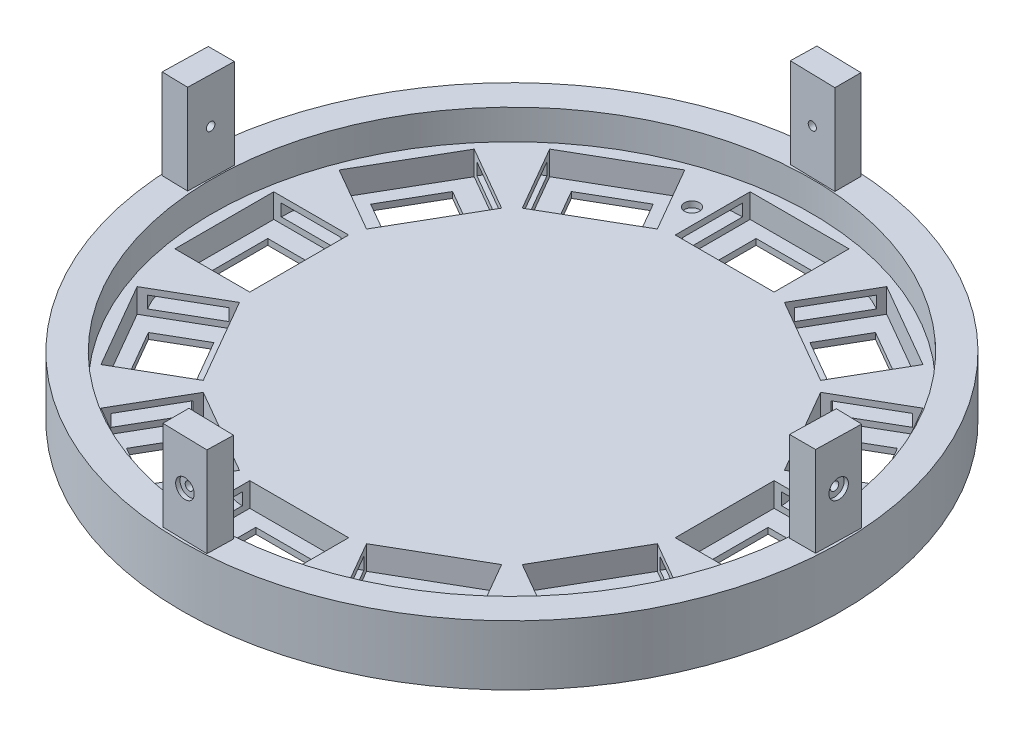
SolidWorks part; units mm, degrees
material "Pine"
ref_plane "Front Plane" through (0, 0, 0) normal (0, 0, 1) x (1, 0, 0)
ref_plane "Top Plane" through (0, 0, 0) normal (0, 1, 0) x (1, 0, 0)
ref_plane "Right Plane" through (0, 0, 0) normal (1, 0, 0) x (0, 0, -1)
sketch "Sketch2" plane through (0, 0, 0) normal (0, 1, 0) x (1, 0, 0)
  circle A0 centre (0, 0) radius 55
  dimension "D1" = 110
extrude "Boss-Extrude1" add sketch "Sketch2" along normal blind 10
sketch "Sketch3" plane through (0, 10, 0) normal (0, 1, 0) x (1, 0, 0)
  circle A3 centre (0, 0) radius 50
  circle A4 centre (0, 0) radius 50
  dimension "D1" = 5
extrude "Cut-Extrude1" cut sketch "Sketch3" against normal blind 5
sketch "Sketch4" plane through (0, 5, 0) normal (0, 1, 0) x (1, 0, 0)
  line L0 (0, 0) -> (0, 50) construction
  line L5 (-8.25, 48) -> (8.25, 48)
  line L6 (-8.25, 48) -> (-8.25, 35.5)
  line L7 (-8.25, 35.5) -> (8.25, 35.5)
  line L8 (8.25, 48) -> (8.25, 35.5)
  line L37 (16.8553, 45.6942) -> (10.6053, 34.8689)
  line L38 (16.8553, 45.6942) -> (31.1447, 37.4442)
  line L39 (31.1447, 37.4442) -> (24.8947, 26.6189)
  line L40 (10.6053, 34.8689) -> (24.8947, 26.6189)
  line L41 (37.4442, 31.1447) -> (26.6189, 24.8947)
  line L42 (37.4442, 31.1447) -> (45.6942, 16.8553)
  line L43 (45.6942, 16.8553) -> (34.8689, 10.6053)
  line L44 (26.6189, 24.8947) -> (34.8689, 10.6053)
  line L45 (48, 8.25) -> (35.5, 8.25)
  line L46 (48, 8.25) -> (48, -8.25)
  line L47 (48, -8.25) -> (35.5, -8.25)
  line L48 (35.5, 8.25) -> (35.5, -8.25)
  line L49 (45.6942, -16.8553) -> (34.8689, -10.6053)
  line L50 (45.6942, -16.8553) -> (37.4442, -31.1447)
  line L51 (37.4442, -31.1447) -> (26.6189, -24.8947)
  line L52 (34.8689, -10.6053) -> (26.6189, -24.8947)
  line L53 (31.1447, -37.4442) -> (24.8947, -26.6189)
  line L54 (31.1447, -37.4442) -> (16.8553, -45.6942)
  line L55 (16.8553, -45.6942) -> (10.6053, -34.8689)
  line L56 (24.8947, -26.6189) -> (10.6053, -34.8689)
  line L57 (8.25, -48) -> (8.25, -35.5)
  line L58 (8.25, -48) -> (-8.25, -48)
  line L59 (-8.25, -48) -> (-8.25, -35.5)
  line L60 (8.25, -35.5) -> (-8.25, -35.5)
  line L61 (-16.8553, -45.6942) -> (-10.6053, -34.8689)
  line L62 (-16.8553, -45.6942) -> (-31.1447, -37.4442)
  line L63 (-31.1447, -37.4442) -> (-24.8947, -26.6189)
  line L64 (-10.6053, -34.8689) -> (-24.8947, -26.6189)
  line L65 (-37.4442, -31.1447) -> (-26.6189, -24.8947)
  line L66 (-37.4442, -31.1447) -> (-45.6942, -16.8553)
  line L67 (-45.6942, -16.8553) -> (-34.8689, -10.6053)
  line L68 (-26.6189, -24.8947) -> (-34.8689, -10.6053)
  line L69 (-48, -8.25) -> (-35.5, -8.25)
  line L70 (-48, -8.25) -> (-48, 8.25)
  line L71 (-48, 8.25) -> (-35.5, 8.25)
  line L72 (-35.5, -8.25) -> (-35.5, 8.25)
  line L73 (-45.6942, 16.8553) -> (-34.8689, 10.6053)
  line L74 (-45.6942, 16.8553) -> (-37.4442, 31.1447)
  line L75 (-37.4442, 31.1447) -> (-26.6189, 24.8947)
  line L76 (-34.8689, 10.6053) -> (-26.6189, 24.8947)
  line L77 (-31.1447, 37.4442) -> (-24.8947, 26.6189)
  line L78 (-31.1447, 37.4442) -> (-16.8553, 45.6942)
  line L79 (-16.8553, 45.6942) -> (-10.6053, 34.8689)
  line L80 (-24.8947, 26.6189) -> (-10.6053, 34.8689)
  circle A0 centre (0, 0) radius 50 construction
  point P10 (0, 48)
  point P42 (0, 0)
  point P58 (0, 0)
  dimension "D4" = 2
  dimension "D2" = 16.5
  dimension "D3" = 12.5
  dimension "D1" = 12
extrude "Cut-Extrude2" cut sketch "Sketch4" against normal blind 4
sketch "Sketch6" plane through (0, 1, 0) normal (0, 1, 0) x (1, 0, 0)
  line L0 (0, 0) -> (0, 50) construction
  line L1 (-5, 37.75) -> (5, 37.75)
  line L2 (-5, 37.75) -> (-5, 45.75)
  line L3 (-5, 45.75) -> (5, 45.75)
  line L4 (5, 37.75) -> (5, 45.75)
  line L5 (-5, 37.75) -> (5, 45.75) construction
  line L6 (-5, 45.75) -> (5, 37.75) construction
  line L7 (-8.25, 41.75) -> (8.25, 41.75) construction
  line L8 (-8.25, 48) -> (-8.25, 35.5) construction
  circle A0 centre (0, 0) radius 50 construction
  point P0 (0, 41.75)
  dimension "D1" = 10
  dimension "D2" = 8
extrude "Cut-Extrude3" cut sketch "Sketch6" against normal through all
pattern_circular "CirPattern1" count 12 over 360 about axis through (0, 5, 0) along (0, 1, 0) of "Cut-Extrude3"
sketch "Sketch7" plane through (-8.25, 0, 0) normal (1, 0, 0) x (0, 0, -1)
  line L0 (41.75, 1) -> (41.75, 5) construction
  line L1 (36.75, 1.9966) -> (46.75, 1.9966)
  line L2 (36.75, 1.9966) -> (36.75, 4.0034)
  line L3 (36.75, 4.0034) -> (46.75, 4.0034)
  line L4 (46.75, 1.9966) -> (46.75, 4.0034)
  line L5 (36.75, 1.9966) -> (46.75, 4.0034) construction
  line L6 (36.75, 4.0034) -> (46.75, 1.9966) construction
  line L7 (48, 1) -> (35.5, 1) construction
  line L8 (48, 5) -> (35.5, 5) construction
  point P0 (41.75, 3)
  dimension "D1" = 10
ref_axis "Axis3" through (-8.25, 1, -30.7894) along (0, 1, 0)
revolve "Cut-Revolve1" cut sketch "Sketch7" angle 31 about axis through (-8.25, 1, -30.7894) along (0, 1, 0)
ref_axis "Axis4" through (0, -0.5, 0) along (0, 1, 0)
pattern_circular "CirPattern8" count 12 over 360 about axis through (0, -0.5, 0) along (0, 1, 0) of "Cut-Revolve1"
sketch "Sketch10" plane through (0, 5, 0) normal (0, 1, 0) x (1, 0, 0)
  circle A0 centre (-10.8945, 40.9446) radius 1.25
  dimension "D1" = 2.5
extrude "Cut-Extrude4" cut sketch "Sketch10" against normal up to next
sketch "Sketch11" plane through (0, 10, 0) normal (0, 1, 0) x (1, 0, 0)
  line L0 (50.291, 3.8348) -> (50.1144, -3.7845)
  line L1 (50.1144, -3.7845) -> (54.4604, -3.7845)
  line L2 (54.4604, -3.7845) -> (54.6347, 3.7341)
  line L3 (54.6347, 3.7341) -> (50.291, 3.8348)
  line L4 (0, 0) -> (55, 0) construction
  line L5 (52.2874, -3.7845) -> (52.4628, 3.7845) construction
  circle A3 centre (0, 0) radius 55 construction
  point P10 (52.3751, 0)
extrude "Boss-Extrude2" add sketch "Sketch11" along normal blind 15
pattern_circular "CirPattern9" count 4 over 360 about axis through (0, -0.5, 0) along (0, 1, 0) of "Boss-Extrude2"
sketch "Sketch13" plane through (1.2638, 0, -54.5188) normal (0.0232, 0, -0.9997) x (-0.9997, 0, -0.0232)
  line L0 (0, 0) -> (0, 21.0762) construction
sketch "Sketch14" plane through (54.5188, 0, 1.2638) normal (0.9997, 0, 0.0232) x (0.0232, 0, -0.9997)
  line L0 (1.239, 10) -> (1.239, 25) construction
  line L1 (-2.5213, 10) -> (4.9993, 10) construction
  line L2 (-2.5213, 25) -> (4.9993, 25) construction
  point P6 (1.239, 17.5)
hole_wizard "CBORE for #00 Binding Head Machine Screw3" positions "3DSketch4" profile "Sketch15" counterbore size "#00" standard "ANSI Inch"
sketch3d "3DSketch4"
  point P0 (54.5475, 17.5, 0.0252)
sketch "Sketch15" plane through (54.5475, 17.5, 0.0252) normal (0, 1, 0) x (0.0232, 0, -0.9997)
  line L0 (0, 0) -> (0, 7.9197)
  line L1 (0, 7.9197) -> (0.6985, 7.5)
  line L2 (0.6985, 7.5) -> (0.6985, 0.7112)
  line L3 (0.6985, 0.7112) -> (1.5875, 0.7112)
  line L4 (1.5875, 0.7112) -> (1.5875, 0)
  line L5 (1.5875, 0) -> (0, 0)
  line L10 (0, 7.9197) -> (-0.6985, 7.5) construction
  line L11 (0, -6.35) -> (0, 107.95) construction
  dimension "Hole Dia." = 1.397
  dimension "Hole Depth" = 7.5
  dimension "C'Bore Dia." = 3.175
  dimension "C'Bore Depth" = 0.7112
  dimension "Drill Angle" = 118
pattern_circular "CirPattern10" count 4 over 360 about axis through (0, -0.5, 0) along (0, 1, 0) of "CBORE for #00 Binding Head Machine Screw3"
